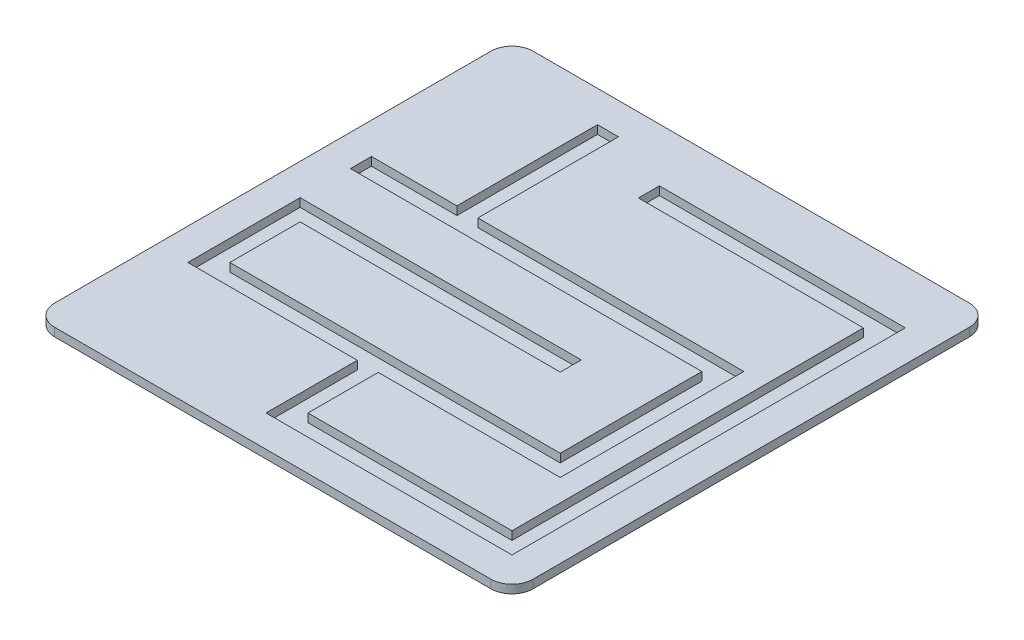
SolidWorks part; units mm, degrees
ref_plane "Front Plane" through (0, 0, 0) normal (0, 0, 1) x (1, 0, 0)
ref_plane "Top Plane" through (0, 0, 0) normal (0, 1, 0) x (1, 0, 0)
ref_plane "Right Plane" through (0, 0, 0) normal (1, 0, 0) x (0, 0, -1)
sketch "Sketch1" plane through (0, 0, 0) normal (0, 1, 0) x (1, 0, 0)
  line L1 (-104, -114) -> (104, -114)
  line L2 (-114, -104) -> (-114, 104)
  line L3 (-104, 114) -> (104, 114)
  line L4 (114, -104) -> (114, 104)
  arc A0 (104, -114) -> (114, -104) centre (104, -104) ccw
  arc A1 (-104, -114) -> (-114, -104) centre (-104, -104) cw
  arc A2 (104, 114) -> (114, 104) centre (104, 104) cw
  arc A3 (-114, 104) -> (-104, 114) centre (-104, 104) cw
  point P0 (0, 0)
  point P6 (-114, 0)
  point P7 (0, 114)
  point P10 (114, -114)
  point P15 (114, 114)
  point P18 (-114, 114)
  dimension "D3" = 10
  dimension "D1" = 228
  dimension "D2" = 228
extrude "Boss-Extrude1" add sketch "Sketch1" along normal blind 4
sketch "Sketch4" plane through (0, 0, 0) normal (0, 1, 0) x (1, 0, 0)
  line L24 (-53.25, 99) -> (-53.25, 32) construction
  line L25 (-58.25, 99) -> (-58.25, 32)
  line L58 (-99, 27) -> (73.5, 27) construction
  line L59 (73.5, 27) -> (73.5, -50.5) construction
  line L60 (73.5, -50.5) -> (-94, -50.5) construction
  line L61 (-94, -50.5) -> (-94, -7) construction
  line L62 (-94, -7) -> (35, -7) construction
  line L63 (-13.25, -55.5) -> (-13.25, -94) construction
  line L64 (-13.25, -94) -> (94, -94) construction
  line L65 (94, -94) -> (94, 83.5) construction
  line L66 (94, 83.5) -> (-18.25, 83.5) construction
  line L68 (-99, 22) -> (68.5, 22)
  line L69 (68.5, 22) -> (68.5, -45.5)
  line L70 (68.5, -45.5) -> (-89, -45.5)
  line L71 (-89, -45.5) -> (-89, -12)
  line L72 (-89, -12) -> (35, -12)
  line L73 (-18.25, -55.5) -> (-18.25, -99)
  line L74 (-18.25, -99) -> (99, -99)
  line L75 (99, -99) -> (99, 88.5)
  line L76 (99, 88.5) -> (-18.25, 88.5)
  line L77 (-48.25, 99) -> (-48.25, 32)
  line L78 (-99, 32) -> (-58.25, 32)
  line L79 (78.5, 32) -> (78.5, -55.5)
  line L80 (78.5, -55.5) -> (-8.25, -55.5)
  line L81 (-99, -55.5) -> (-99, -2)
  line L82 (-99, -2) -> (35, -2)
  line L83 (-8.25, -55.5) -> (-8.25, -89)
  line L84 (-8.25, -89) -> (89, -89)
  line L85 (89, -89) -> (89, 78.5)
  line L86 (89, 78.5) -> (-18.25, 78.5)
  line L87 (-58.25, 99) -> (-48.25, 99)
  line L89 (-99, 22) -> (-99, 32)
  line L90 (35, -12) -> (35, -2)
  line L92 (-18.25, 88.5) -> (-18.25, 78.5)
  line L93 (-48.25, 99) -> (-48.25, 49.8251) construction
  line L94 (-53.25, 99) -> (-53.25, 49.8251) construction
  line L95 (-58.25, 99) -> (-58.25, 49.8251) construction
  line L96 (-8.25, 11.0765) -> (-8.25, -89) construction
  line L97 (-13.25, 11.0765) -> (-13.25, -94) construction
  line L98 (-18.25, 11.0765) -> (-18.25, -99) construction
  line L99 (-18.25, -55.5) -> (-99, -55.5)
  line L100 (78.5, -55.5) -> (-99, -55.5) construction
  line L101 (-48.25, 32) -> (78.5, 32)
  line L102 (-99, 32) -> (78.5, 32) construction
  line L103 (-114, 104) -> (-114, -104) construction
  line L104 (104, 114) -> (-104, 114) construction
  line L105 (114, -104) -> (114, 104) construction
  line L106 (-104, -114) -> (104, -114) construction
  dimension "D1" = 5
  dimension "D2" = 5
  dimension "D3" = 15
  dimension "D4" = 15
  dimension "D5" = 15
  dimension "D6" = 15
  dimension "D7" = 67
  dimension "D8" = 167.5
  dimension "D9" = 134
  dimension "D11" = 117.25
  dimension "D13" = 33.5
  dimension "D14" = 117.25
  dimension "D10" = 33.5
  dimension "D12" = 167.5
  dimension "D15" = 30
extrude "Cut-Extrude3" cut sketch "Sketch4" along normal blind 12
extrude "Boss-Extrude6" add sketch "Sketch4<5>" against normal blind 10 separate body
sketch "Sketch4<5>" plane through (0, 0, 0) normal (0, 1, 0) x (1, 0, 0) same geometry as "Sketch4"
equation "\"6_lights\"=100.5"
equation "\"3_lights\"=50.25"
equation "\"4_lights\"=67"
equation "\"5_lights\"=83.75"
equation "\"12_lights\"=201"
equation "\"10_lights\"=167.5"
equation "\"7_lights\"=117.25"
equation "\"11_lights\"=184.25"
equation "\"8_lights\"=134"
equation "\"2_lights\"=33.5"
